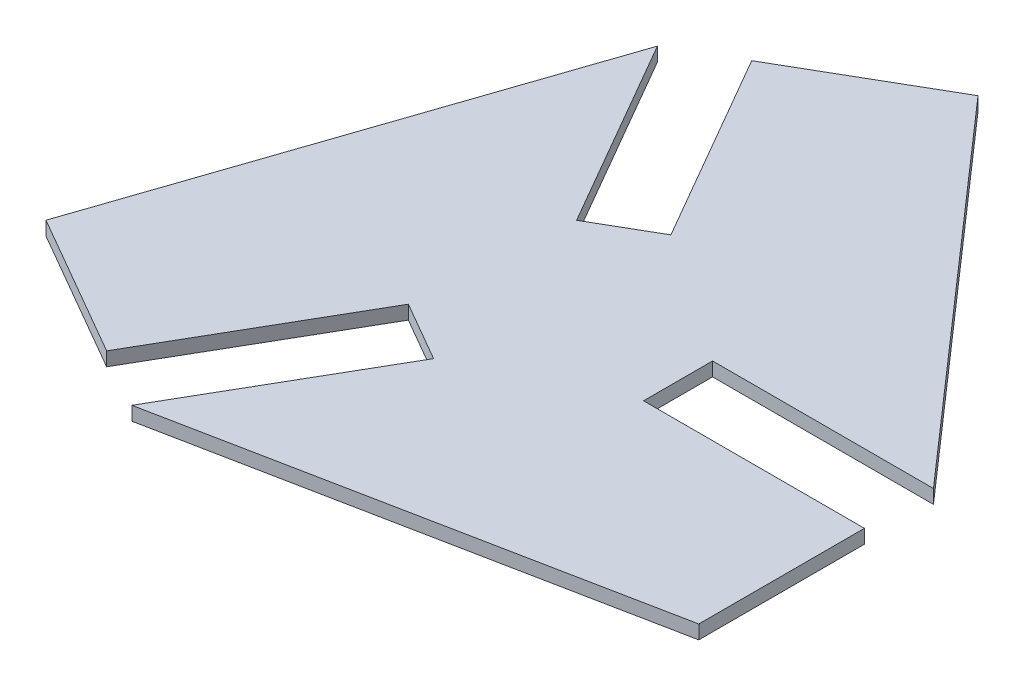
SolidWorks part; units mm, degrees
ref_plane "Front Plane" through (0, 0, 0) normal (0, 0, 1) x (1, 0, 0)
ref_plane "Top Plane" through (0, 0, 0) normal (0, 1, 0) x (1, 0, 0)
ref_plane "Right Plane" through (0, 0, 0) normal (1, 0, 0) x (0, 0, -1)
sketch "Sketch1" plane through (0, 0, 0) normal (0, 1, 0) x (1, 0, 0)
  line L0 (76.2, -47.5615) -> (76.2, 6.4135) construction
  line L1 (76.2, -47.5615) -> (-32.5457, -69.1979)
  line L2 (-43.6543, 62.7844) -> (-79.2895, -42.2104)
  line L5 (-79.2895, -42.2104) -> (-32.5457, -69.1979) construction
  line L6 (76.2, 6.4135) -> (25.4, 6.4135)
  line L7 (25.4, 6.4135) -> (25.4, -9.4615)
  line L8 (25.4, -9.4615) -> (76.2, -9.4615)
  line L9 (76.2, -9.4615) -> (76.2, -47.5615)
  line L10 (3.0895, 89.7719) -> (76.2, 6.4135)
  line L11 (-46.2939, -61.2604) -> (-79.2895, -42.2104)
  line L12 (-20.8939, -17.2663) -> (-46.2939, -61.2604)
  line L13 (-32.5457, -69.1979) -> (-7.1457, -25.2038)
  line L14 (-7.1457, -25.2038) -> (-20.8939, -17.2663)
  line L16 (3.0895, 89.7719) -> (-43.6543, 62.7844) construction
  line L17 (-29.9061, 70.7219) -> (3.0895, 89.7719)
  line L18 (-4.5061, 26.7278) -> (-29.9061, 70.7219)
  line L19 (-43.6543, 62.7844) -> (-18.2543, 18.7903)
  line L20 (-18.2543, 18.7903) -> (-4.5061, 26.7278)
  line L21 (0, 0) -> (-49999.9986, 0) construction
  line L22 (0, 0) -> (-25000, 43301.2702) construction
  line L23 (0, 0) -> (-25000, -43301.2702) construction
  line L24 (25.4, 0) -> (76.2, 0) construction
  line L25 (-12.7, -21.997) -> (-38.1, -65.9911) construction
  line L26 (-12.7, 21.997) -> (-38.1, 65.9911) construction
  line L27 (76.2, 8.001) -> (76.2, 45.974) [skipped]
  line L28 (-31.1709, -69.9916) -> (1.7147, -88.9781) [skipped]
  line L29 (-45.0291, 61.9906) -> (-77.9147, 43.0041) [skipped]
  circle A1 centre (0, 0) radius 76.2 construction
  point P31 (-62.7917, -51.7354)
  dimension "D2" = 15.875
  dimension "D6" = 152.4
  dimension "D1" = 120
  dimension "D3" = 50.8
  dimension "D4" = 38.1
  dimension "D5" = 3
  dimension "D7" = 9.4615
  dimension "D9" = 120
  dimension "D10" = 120
  dimension "D8" = 3
extrude "Boss-Extrude2" add sketch "Sketch1" along normal blind 3.175
